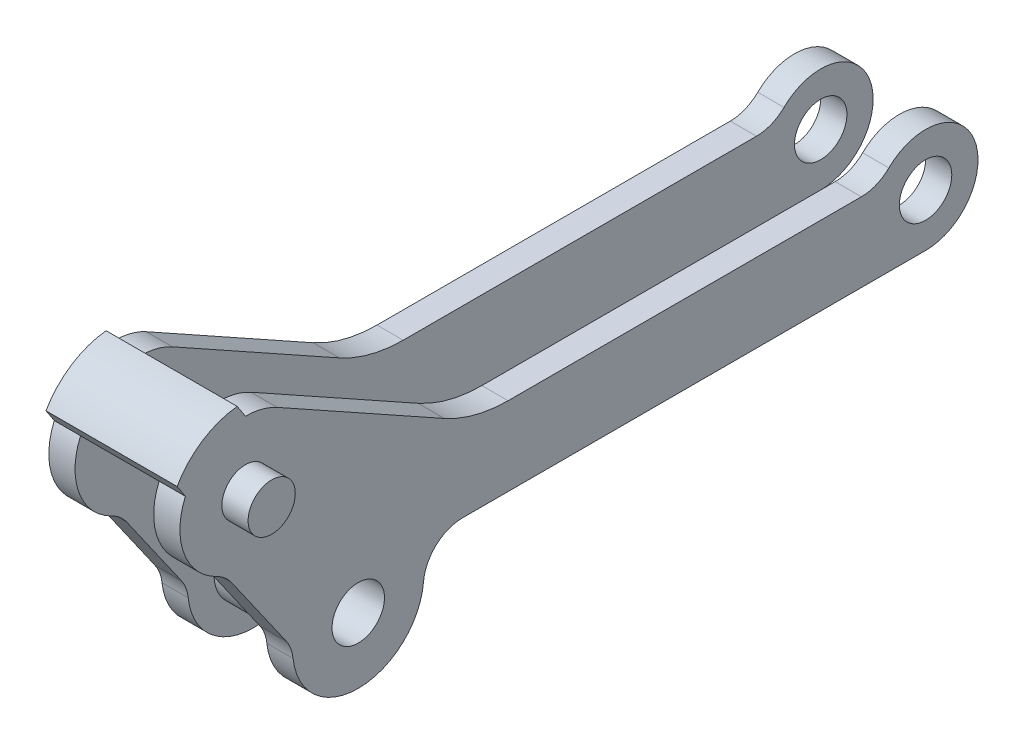
SolidWorks part; units mm, degrees
ref_plane "前视基准面" through (0, 0, 0) normal (0, 0, 1) x (1, 0, 0)
ref_plane "上视基准面" through (0, 0, 0) normal (0, 1, 0) x (1, 0, 0)
ref_plane "右视基准面" through (0, 0, 0) normal (1, 0, 0) x (0, 0, -1)
other "Configuration Table"
sketch "草图1" plane through (0, 0, 0) normal (1, 0, 0) x (0, 0, -1)
  line L1 (0, 0) -> (44.2012, 0)
  line L2 (0, 0) -> (4.2012, -6)
  line L3 (4.2012, -6) -> (44.2012, -6)
  line L4 (44.2012, 0) -> (44.2012, -6)
  line L5 (-10.9556, 1.6987) -> (-4.4024, 6.2873)
  line L6 (-10.9556, 1.6987) -> (-2.352, -10.5886)
  line L7 (-2.352, -10.5886) -> (4.2012, -6)
  line L8 (-4.4024, 6.2873) -> (4.2012, -6)
  circle A0 centre (-7.679, 3.993) radius 5
  circle A1 centre (0.9246, -8.2943) radius 5
  circle A3 centre (44.2012, -2) radius 4
  circle A4 centre (-7.679, 3.993) radius 2
  circle A5 centre (44.2012, -2) radius 2
  circle A6 centre (0.9246, -8.2943) radius 2
  circle A7 centre (0.9246, -8.2943) radius 3
  dimension "D5" = 10
  dimension "D6" = 10
  dimension "D8" = 8
  dimension "D9" = 4
  dimension "D10" = 6
  dimension "D1" = 125
  dimension "D2" = 40
  dimension "D3" = 6
  dimension "D4" = 8
  dimension "D7" = 15
extrude "凸台-拉伸1" add sketch "草图1" along normal blind 2 contours A3 L1 L2 A1 L3 | A0 | L8 L5 L6 L7 | A1 | A3 region at (0, -2.9524, -21.636)
extrude "凸台-拉伸2" add sketch "草图1<4>" against normal blind 2 contours A7
sketch "草图1<4>" plane through (0, 0, 0) normal (1, 0, 0) x (0, 0, -1) same geometry as "草图1"
extrude "切除-拉伸1" cut sketch "草图1<3>" along normal through all both and the other way through all contours A4 | A6 | A5
sketch "草图1<3>" plane through (0, 0, 0) normal (1, 0, 0) x (0, 0, -1) same geometry as "草图1"
fillet "圆角1" radius 3 5 edges at (1, 0, -40.7371) (1, -8.1312, 4.0727) (1, -0.7588, 9.2349) (1, -6, -5.3672) (1, 0, 0)
sketch "草图2" plane through (2, 0, 0) normal (1, 0, 0) x (0, 0, -1)
  circle A0 centre (-7.679, 3.993) radius 2
  circle A1 centre (-7.679, 3.993) radius 1.8
  circle A2 centre (-7.679, 3.993) radius 2 construction
  dimension "D1" = 3.6
extrude "凸台-拉伸3" add sketch "草图2" against normal up to surface (2 mm away) contours A0 up to face at (0, 3.993, 5.679)
extrude "凸台-拉伸4" add sketch "草图2<3>" along normal blind 2 contours A1 region at (2, 3.993, 7.679)
sketch "草图2<3>" plane through (2, 0, 0) normal (1, 0, 0) x (0, 0, -1) same geometry as "草图2"
ref_plane "基准面1" through (-3, 0, 0) normal (-1, 0, 0) x (0, 0, 1)
sketch "草图4" plane through (2, 0, 0) normal (1, 0, 0) x (0, 0, -1)
  line L0 (-5.2448, 8.3604) -> (9.7552, 0)
  line L1 (1.5617, 0) -> (39.3023, 0) construction
  line L5 (-5.2448, 0) -> (-5.2448, 8.3604)
  line L6 (-5.2448, 0) -> (9.7552, 0)
  arc A2 (-2.6817, 3.8298) -> (-9.8744, -0.4993) centre (-7.679, 3.993) ccw construction
  point P2 (-4.7476, 8.0435)
  point P8 (6.3931, 0)
  point P9 (-10.2574, 8.2769)
  dimension "D1" = 15
extrude "凸台-拉伸6" add sketch "草图4" against normal blind 2
sketch "草图3" plane through (2, 0, 0) normal (1, 0, 0) x (0, 0, -1)
  line L0 (-7.679, 3.993) -> (-16.6015, 16.7356) construction
  line L1 (-8.7342, -1.4739) -> (-4.5734, -7.416) construction
  line L2 (-19.3045, 5.993) -> (3.1525, 5.993) construction
  line L7 (-7.679, 8.993) -> (-12.2616, 5.993) construction
  line L8 (-12.2616, 5.993) -> (-13.2566, 7.5129)
  line L9 (9.7552, 0) -> (39.3023, 0) construction
  line L10 (-13.2566, 7.5129) -> (-8.6741, 10.5129) construction
  line L11 (-8.6741, 10.5129) -> (-7.679, 8.993)
  circle A0 centre (-7.679, 3.993) radius 5
  arc A1 (-5.2448, 8.3604) -> (-9.8744, -0.4993) centre (-7.679, 3.993) ccw construction
  circle A2 centre (-7.679, 3.993) radius 2
  circle A3 centre (0.9246, -8.2943) radius 2 construction
  circle A4 centre (-7.679, 3.993) radius 6
  point P7 (-14.0836, 13.1397)
  arc M18 (-5.2448, 8.3604) -> (-9.8744, -0.4993) centre (-7.679, 3.993) ccw
  dimension "D1" = 12
extrude "凸台-拉伸5" add sketch "草图3" against normal up to surface (5 mm away) contours L11 A4 L8 M18 region at (2, 8.3868, 10.5555) up to plane "基准面1"
fillet "圆角3" radius 10 1 edges at (1, 0, -9.7552)
mirror "镜向1" about plane through (-3, 0, 0) normal (-1, 0, 0) of bodies 111
